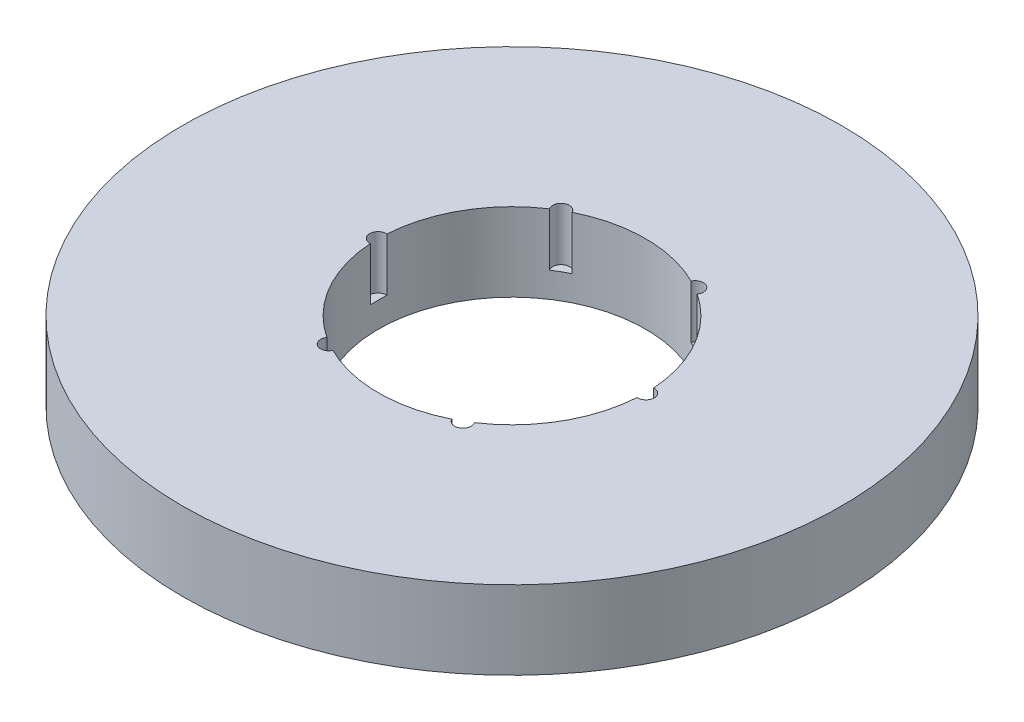
SolidWorks part; units mm, degrees
ref_plane "Front Plane" through (0, 0, 0) normal (0, 0, 1) x (1, 0, 0)
ref_plane "Top Plane" through (0, 0, 0) normal (0, 1, 0) x (1, 0, 0)
ref_plane "Right Plane" through (0, 0, 0) normal (1, 0, 0) x (0, 0, -1)
sketch "Sketch1" plane through (0, 0, 0) normal (0, 1, 0) x (1, 0, 0)
  circle A0 centre (0, 0) radius 92.5
  dimension "FLANGE_OD" = 185
extrude "Boss-Extrude1" add sketch "Sketch1" along normal blind 22
sketch "Sketch2" plane through (0, 0, 0) normal (0, 1, 0) x (1, 0, 0)
  circle A0 centre (0, 0) radius 37.5
  dimension "BORE_D" = 75
extrude "Cut-Extrude1" cut sketch "Sketch2" along normal through all
sketch "Sketch3" plane through (0, 22, 0) normal (0, 1, 0) x (1, 0, 0)
  circle A0 centre (0, 0) radius 37.6098 construction
  circle A1 centre (-37.6098, 0) radius 2.3292
  dimension "BOLT_D" = 4.6584
  dimension "BOLT_PCD" = 75.2195
extrude "Cut-Extrude2" cut sketch "Sketch3" against normal blind 14.9172
pattern_circular "CirPattern1" count 6 over 360 about axis through (0, 0, 0) along (0, 1, 0) of "Cut-Extrude2"
